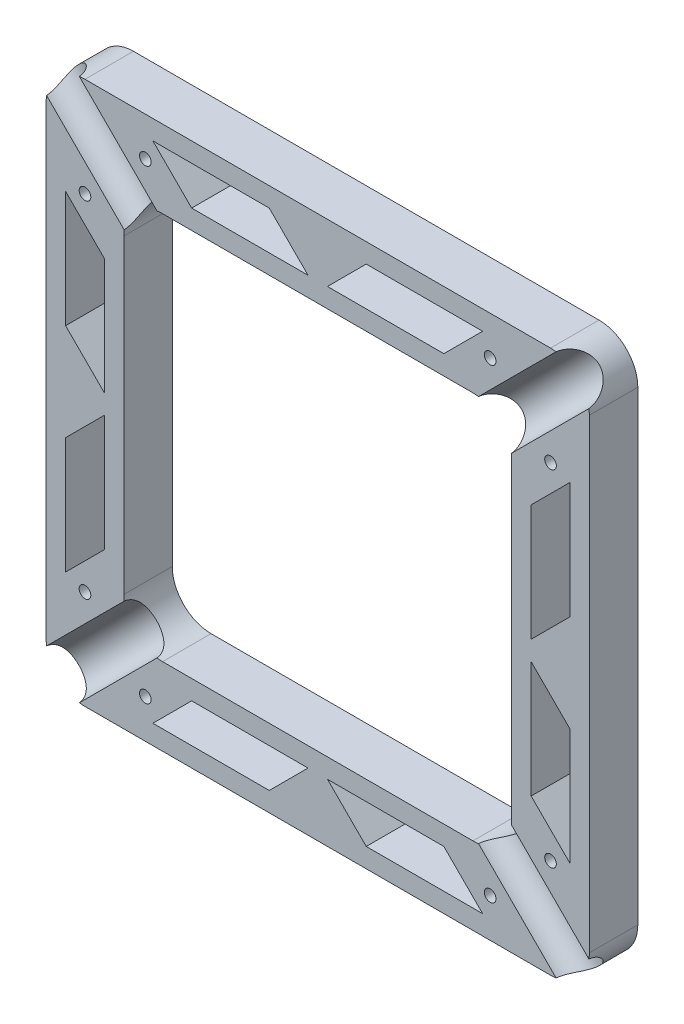
SolidWorks part; units mm, degrees
ref_plane "Plan de face" through (0, 0, 0) normal (0, 0, 1) x (1, 0, 0)
ref_plane "Plan de dessus" through (0, 0, 0) normal (0, 1, 0) x (1, 0, 0)
ref_plane "Plan de droite" through (0, 0, 0) normal (1, 0, 0) x (0, 0, -1)
sketch "Esquisse1" plane through (0, 0, 0) normal (0, 0, 1) x (1, 0, 0)
  line L0 (55, 75.9996) -> (55, -81.4607) construction
  line L1 (-70, 70) -> (70, 70)
  line L2 (-70, 70) -> (-70, -70)
  line L3 (-70, -70) -> (70, -70)
  line L4 (70, 70) -> (70, -70)
  line L5 (-50, 50) -> (50, 50)
  line L6 (-50, 50) -> (-50, -50)
  line L7 (-50, -50) -> (50, -50)
  line L8 (50, 50) -> (50, -50)
  line L9 (65, 75.9996) -> (65, -81.4607) construction
  line L10 (50, 0) -> (70, 0) construction
  line L11 (52.5, 0) -> (65, 12.5) construction
  line L12 (65, 12.5) -> (55, 2.5)
  line L13 (65, -12.5) -> (52.5, 0) construction
  line L14 (65, -12.5) -> (55, -2.5)
  line L15 (65, -12.5) -> (65, -42.5)
  line L16 (65, -42.5) -> (55, -32.5)
  line L17 (55, -32.5) -> (55, -2.5)
  line L18 (65, 12.5) -> (65, 42.5)
  line L19 (65, 42.5) -> (55, 32.5)
  line L20 (55, 32.5) -> (55, 2.5)
  line L21 (12.5, -65) -> (2.5, -55)
  line L22 (-12.5, -65) -> (-2.5, -55)
  line L23 (-12.5, -65) -> (-42.5, -65)
  line L24 (-42.5, -65) -> (-32.5, -55)
  line L25 (-32.5, -55) -> (-2.5, -55)
  line L26 (12.5, -65) -> (42.5, -65)
  line L27 (42.5, -65) -> (32.5, -55)
  line L28 (32.5, -55) -> (2.5, -55)
  line L29 (0, -52.5) -> (12.5, -65) construction
  line L30 (-12.5, -65) -> (0, -52.5) construction
  line L31 (-65, -12.5) -> (-55, -2.5)
  line L32 (-65, 12.5) -> (-55, 2.5)
  line L33 (-65, 12.5) -> (-65, 42.5)
  line L34 (-65, 42.5) -> (-55, 32.5)
  line L35 (-55, 32.5) -> (-55, 2.5)
  line L36 (-65, -12.5) -> (-65, -42.5)
  line L37 (-65, -42.5) -> (-55, -32.5)
  line L38 (-55, -32.5) -> (-55, -2.5)
  line L39 (-52.5, 0) -> (-65, -12.5) construction
  line L40 (-65, 12.5) -> (-52.5, 0) construction
  line L41 (-12.5, 65) -> (-2.5, 55)
  line L42 (12.5, 65) -> (2.5, 55)
  line L43 (12.5, 65) -> (42.5, 65)
  line L44 (42.5, 65) -> (32.5, 55)
  line L45 (32.5, 55) -> (2.5, 55)
  line L46 (-12.5, 65) -> (-42.5, 65)
  line L47 (-42.5, 65) -> (-32.5, 55)
  line L48 (-32.5, 55) -> (-2.5, 55)
  line L49 (0, 52.5) -> (-12.5, 65) construction
  line L50 (12.5, 65) -> (0, 52.5) construction
  dimension "D1" = 140
  dimension "D2" = 140
  dimension "D3" = 70
  dimension "D4" = 70
  dimension "D5" = 20
  dimension "D6" = 20
  dimension "D7" = 100
  dimension "D8" = 100
  dimension "D9" = 5
  dimension "D10" = 5
  dimension "D11" = 2.5
  dimension "D12" = 12.5
  dimension "D13" = 30
  dimension "D14" = 30
  dimension "D15" = 30
  dimension "D16" = 30
  dimension "D17" = 4
extrude "Boss.-Extru.1" add sketch "Esquisse1" along normal blind 12.5
ref_plane "Plan1" through (0, 0, 0) normal (-0.7071, 0.7071, 0) x (-0.7071, -0.7071, 0)
sketch "Esquisse2" plane through (0, 0, 0) normal (-0.7071, 0.7071, 0) x (-0.7071, -0.7071, 0)
  line L0 (99.7696, 13) -> (-97.6372, 13) construction
  line L1 (-6, 13) -> (6, 13)
  arc A0 (-6, 13) -> (6, 13) centre (0, 13) ccw
  dimension "D1" = 13
extrude "Enlèv. mat.-Extru.1" cut sketch "Esquisse2" against normal blind 100 and the other way blind 100
ref_axis "Axe1" through (0, 0, -62.842) along (0, 0, 1)
pattern_circular "Répétition circulaire1" count 2 every 90 about axis through (0, 0, -62.842) along (0, 0, 1) of "Enlèv. mat.-Extru.1"
fillet "Congé1" radius 10 8 edges at (-50, -50, 3.5) (50, -50, 3.5) (-70, 70, 3.5) (50, 50, 3.5) (-50, 50, 3.5) (-70, -70, 3.5) (70, 70, 3.5) (70, -70, 3.5)
sketch "Esquisse3" plane through (0, 0, 12.5) normal (0, 0, 1) x (1, 0, 0)
  line L0 (-60, -70) -> (60, -70) construction
  line L1 (-70, 60) -> (-70, -60) construction
  line L2 (45.3482, 45.3482) -> (-45.3482, -45.3482) construction
  circle A0 centre (-60, -44.4437) radius 1.5
  circle A1 centre (-44.4437, -60) radius 1.5
  circle A2 centre (-44.4437, 60) radius 1.5
  circle A3 centre (-60, 44.4437) radius 1.5
  circle A4 centre (60, 44.4437) radius 1.5
  circle A5 centre (44.4437, 60) radius 1.5
  circle A6 centre (44.4437, -60) radius 1.5
  circle A7 centre (60, -44.4437) radius 1.5
  dimension "D1" = 3
  dimension "D2" = 3
  dimension "D3" = 10
  dimension "D4" = 10
  dimension "D5" = 11
  dimension "D6" = 11
  dimension "D7" = 4
extrude "Enlèv. mat.-Extru.2" cut sketch "Esquisse3" against normal blind 13
